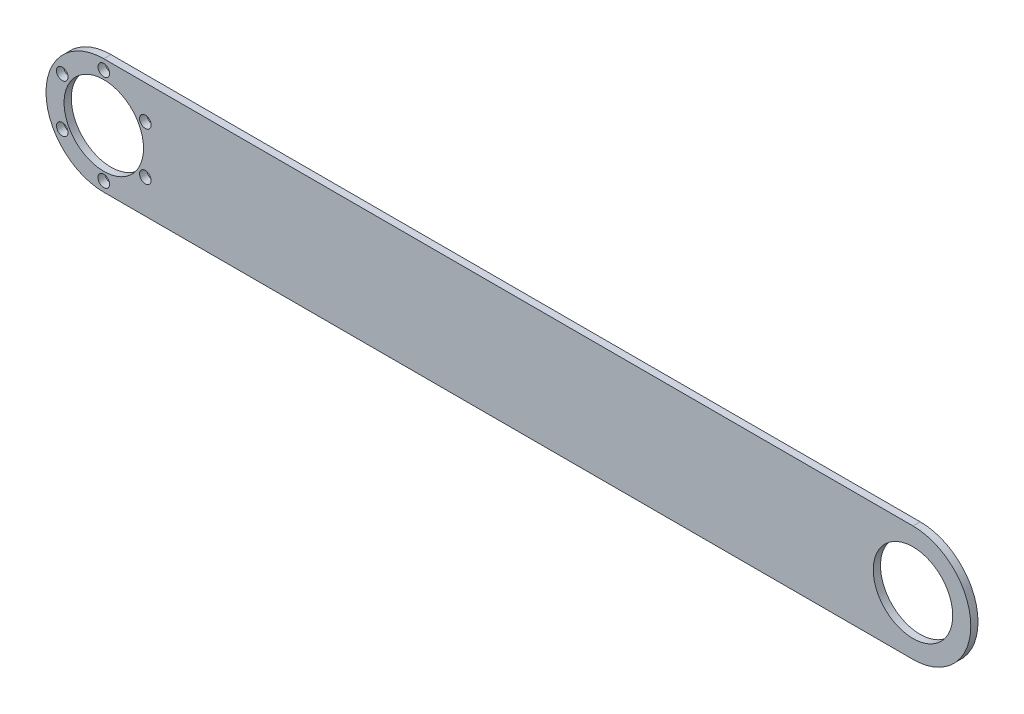
SolidWorks part; units mm, degrees
ref_plane "Front Plane" through (0, 0, 0) normal (0, 0, 1) x (1, 0, 0)
ref_plane "Top Plane" through (0, 0, 0) normal (0, 1, 0) x (1, 0, 0)
ref_plane "Right Plane" through (0, 0, 0) normal (1, 0, 0) x (0, 0, -1)
sketch "Sketch1" plane through (0, 0, 0) normal (0, 0, 1) x (1, 0, 0)
  line L1 (0, 0) -> (355.6, 0)
  line L3 (0, 50.8) -> (355.6, 50.8)
  arc A0 (0, 50.8) -> (0, 0) centre (0, 25.4) ccw
  arc A1 (355.6, 0) -> (355.6, 50.8) centre (355.6, 25.4) ccw
  dimension "D1" = 355.6
  dimension "D2" = 50.8
extrude "Boss-Extrude1" add sketch "Sketch1" along normal blind 3.175
sketch "Sketch2" plane through (0, 0, 3.175) normal (0, 0, 1) x (1, 0, 0)
  circle A0 centre (0, 25.4) radius 17.4625
  arc A1 (0, 50.8) -> (0, 0) centre (0, 25.4) ccw construction
  circle A3 centre (355.6, 25.4) radius 17.4625
  arc A5 (355.6, 0) -> (355.6, 50.8) centre (355.6, 25.4) ccw construction
  dimension "D1" = 34.925
  dimension "D2" = 34.925
extrude "Cut-Extrude1" cut sketch "Sketch2" against normal through all
sketch "Sketch4" plane through (0, 0, 3.175) normal (0, 0, 1) x (1, 0, 0)
  point P0 (0, 46.482)
  point P4 (0, 25.4)
  point P5 (18.2575, 35.941)
  point P7 (18.2575, 14.859)
  point P8 (0, 4.318)
  point P9 (-18.2575, 14.859)
  point P10 (-18.2575, 35.941)
  point P11 (0, 25.4)
  dimension "D1" = 21.082
  dimension "D2" = 6
hole_wizard "#10 Clearance Hole1" positions "3DSketch2" profile "Sketch5" hole size "#10" standard "ANSI Inch" end condition through all
sketch3d "3DSketch2"
  point P0 (18.2575, 35.941, 3.175)
  point P3 (18.2575, 14.859, 3.175)
  point P6 (0, 4.318, 3.175)
  point P9 (-18.2575, 14.859, 3.175)
  point P12 (-18.2575, 35.941, 3.175)
  point P15 (0, 46.482, 3.175)
sketch "Sketch5" plane through (18.2575, 35.941, 3.175) normal (1, 0, 0) x (0, -1, 0)
  line L0 (0, 0) -> (0, 3.175)
  line L1 (0, 3.175) -> (2.5527, 3.175)
  line L2 (2.5527, 3.175) -> (2.5527, 0)
  line L5 (2.5527, 0) -> (0, 0)
  line L11 (0, -6.35) -> (0, 107.95) construction
  dimension "Thru Hole Dia." = 5.1054
  dimension "Thru Hole Depth" = 3.175
ref_axis "Axis1" through (177.8, 50.8, 0) along (0, -0.9981, 0.0624)
ref_plane "Plane1" through (177.8, 0, 0) normal (1, 0, 0) x (0, 0, -1)
